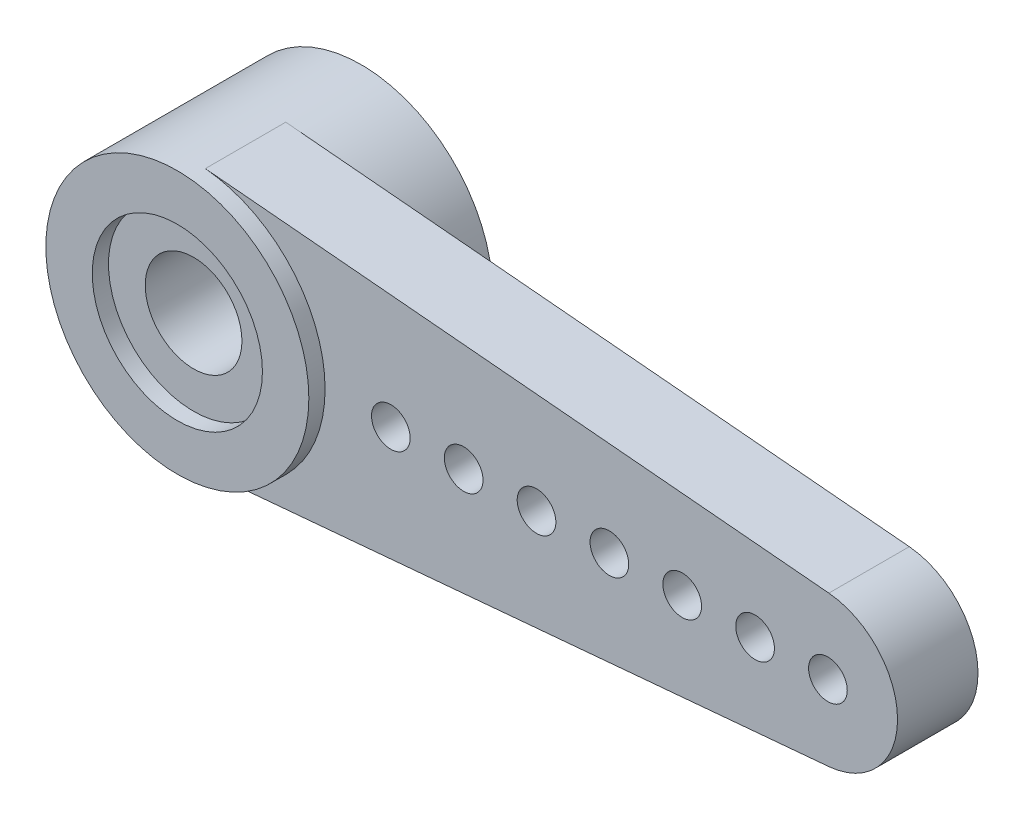
SolidWorks part; units mm, degrees
ref_plane "Front Plane" through (0, 0, 0) normal (0, 0, 1) x (1, 0, 0)
ref_plane "Top Plane" through (0, 0, 0) normal (0, 1, 0) x (1, 0, 0)
ref_plane "Right Plane" through (0, 0, 0) normal (1, 0, 0) x (0, 0, -1)
sketch "Sketch1" plane through (0, 0, 0) normal (0, 0, 1) x (1, 0, 0)
  line L0 (18.2, -5.1547) -> (18.2, 5.1547) construction
  line L1 (-3.4, -4.0329) -> (-3.4, 4.0329) construction
  line L2 (16.424, 1.9422) -> (0.3034, 3.3864)
  line L3 (16.424, -1.9422) -> (0.3034, -3.3864)
  line L4 (16.9, 0.7754) -> (16.9, -0.9477) construction
  circle A0 centre (0, 0) radius 3.4
  arc A1 (16.424, -1.9422) -> (16.424, 1.9422) centre (16.25, 0) ccw
  circle A2 centre (5.1, 0) radius 0.5
  circle A9 centre (6.9833, 0) radius 0.5
  circle A10 centre (8.8667, 0) radius 0.5
  circle A11 centre (10.75, 0) radius 0.5
  circle A12 centre (12.6333, 0) radius 0.5
  circle A13 centre (14.5167, 0) radius 0.5
  circle A14 centre (16.4, 0) radius 0.5
  circle A15 centre (0, 0) radius 2.2
  circle A16 centre (0, 0) radius 1.25
  point P5 (18.2, 0)
  point P8 (-3.4, 0)
  dimension "D1" = 6.8
  dimension "D3" = 3.9
  dimension "D4" = 7
  dimension "D6" = 1
  dimension "D9" = 2.5
  dimension "D2" = 21.6
  dimension "D5" = 1.3
  dimension "D7" = 11.3
  dimension "D8" = 1.2
extrude "Base" add sketch "Sketch1" along normal blind 2.08 contours L3 A1 L2 A0 A14 A13 A12 A11 A10 A9 A2 | A0 A15 | A15 A16 region at (9.5091, 0, 0) region at (2.4382, 2.2295, 0) region at (-2.1378, 0, 0)
extrude "Connection" add sketch "Sketch1<3>" along normal blind 2.5 and the other way blind 2.25 contours A0 A15 region at (2.4382, 2.2295, 0)
sketch "Sketch1<3>" plane through (0, 0, 0) normal (0, 0, 1) x (1, 0, 0) same geometry as "Sketch1"
sketch "Sketch2" plane through (0, 0, 0) normal (0, 0, 1) x (1, 0, 0)
  line L1 (4.3667, -0.75) -> (13.3667, -0.75)
  line L2 (4.3667, -0.75) -> (4.3667, 0.75)
  line L3 (4.3667, 0.75) -> (13.3667, 0.75)
  line L4 (13.3667, -0.75) -> (13.3667, 0.75)
  line L5 (4.3667, -0.75) -> (13.3667, 0.75) construction
  line L6 (4.3667, 0.75) -> (13.3667, -0.75) construction
  point P0 (8.8667, 0)
  dimension "D1" = 1.5
  dimension "D2" = 9
extrude "RectangleCut" [suppressed] cut sketch "Sketch2" along normal through all
